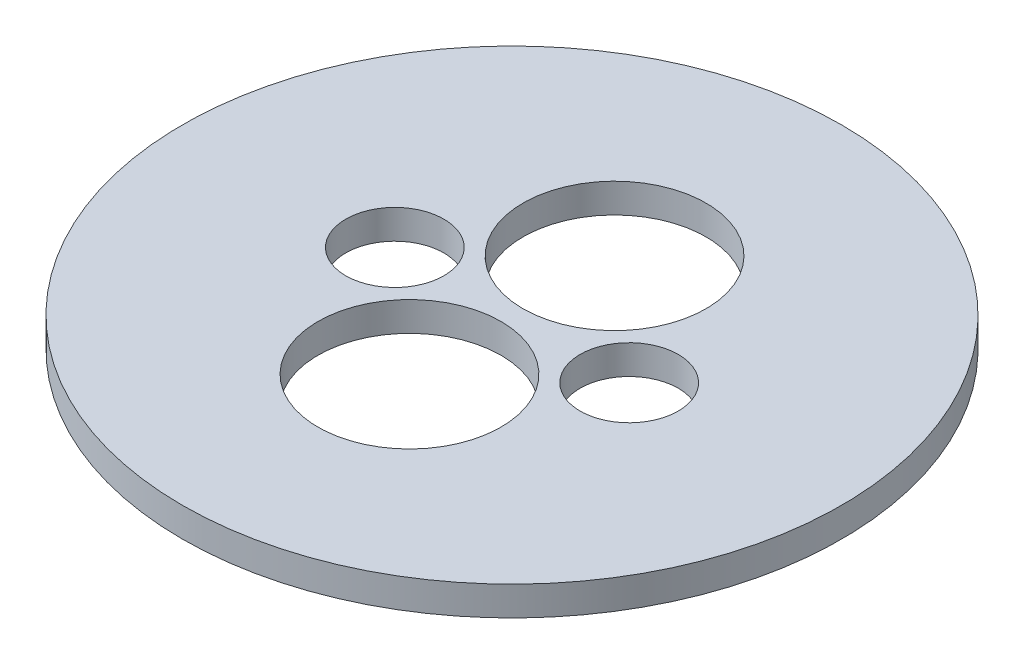
SolidWorks part; units mm, degrees
ref_plane "Front Plane" through (0, 0, 0) normal (0, 0, 1) x (1, 0, 0)
ref_plane "Top Plane" through (0, 0, 0) normal (0, 1, 0) x (1, 0, 0)
ref_plane "Right Plane" through (0, 0, 0) normal (1, 0, 0) x (0, 0, -1)
sketch "Sketch1" plane through (0, 0, 0) normal (0, 1, 0) x (1, 0, 0)
  line L0 (-55, 0) -> (55, 0) construction
  line L1 (0, -55) -> (0, 55) construction
  circle A0 centre (0, 0) radius 1125
  circle A1 centre (0, 0) radius 847.6 construction
  circle A2 centre (0, 350) radius 312.5
  circle A3 centre (-400, 0) radius 167.5
  circle A4 centre (0, -350) radius 312.5
  circle A5 centre (400, 0) radius 167.5
  dimension "D1" = 2250
  dimension "D2" = 1695.2
  dimension "D3" = 335
  dimension "D4" = 625
  dimension "D5" = 350
  dimension "D6" = 400
extrude "Boss-Extrude1" add sketch "Sketch1" along normal blind 100
